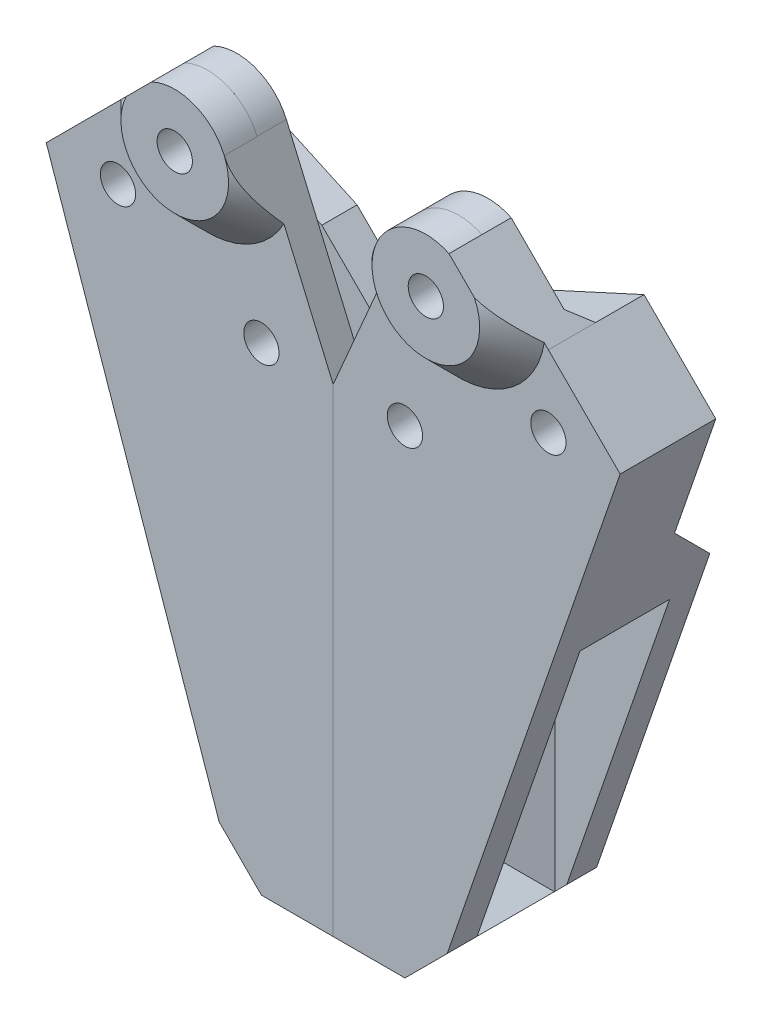
SolidWorks part; units mm, degrees
material "ABS"
ref_plane "Płaszczyzna przednia" through (0, 0, 0) normal (0, 0, 1) x (1, 0, 0)
ref_plane "Płaszczyzna górna" through (0, 0, 0) normal (0, 1, 0) x (1, 0, 0)
ref_plane "Płaszczyzna prawa" through (0, 0, 0) normal (1, 0, 0) x (0, 0, -1)
sketch "Szkic1" plane through (0, 0, 0) normal (0, 0, 1) x (1, 0, 0)
  line L0 (-24, 11) -> (-24, 23)
  line L1 (-24, 11) -> (-36, 11)
  line L2 (-24, 23) -> (-36, 11)
  line L3 (0, 0) -> (0, 12)
  line L4 (0, 12) -> (-24, 23)
  line L5 (0, 0) -> (12, 0)
  line L6 (0, 12) -> (12, 0)
  line L7 (0, 0) -> (0, -80)
  line L8 (0, -80) -> (12, -80)
  line L9 (0, -80) -> (-7.0711, -72.9289)
  line L10 (-7.0711, -72.9289) -> (-36, 11)
  line L11 (12, -80) -> (12, 0)
  circle A0 centre (0, 0) radius 2.95
  circle A1 centre (-24, 11) radius 2.95
  dimension "D1" = 5.9
  dimension "D2" = 24
  dimension "D3" = 5.9
  dimension "D4" = 11
  dimension "D5" = 12
  dimension "D6" = 12
  dimension "D7" = 12
  dimension "D8" = 12
  dimension "D9" = 80
  dimension "D10" = 12
  dimension "D11" = 135
  dimension "D12" = 10
extrude "Dodanie-wyciągnięcie1" add sketch "Szkic1" along normal blind 25 contours A1 L0 L2 L1 | A1 L1 L10 L9 L7 A0 L3 L4 L0 | A0 L5 L6 L3 | A0 L7 L8 L11 L5 region at (-28.2882, 15.2882, 0) region at (-12.4584, -19.8234, 0) region at (4.2882, 4.2882, 0) region at (6.034, -40.2779, 0)
sketch "Szkic3" plane through (12, 0, 0) normal (1, 0, 0) x (0, 0, -1)
  line L0 (-20.1, 17) -> (-20.1, -8)
  line L1 (-25, -80) -> (-25, 0) construction
  line L2 (-14.9, 17) -> (-14.9, -8)
  line L3 (-9, 17) -> (-9, -8)
  line L4 (-4, 17) -> (-4, -8)
  line L5 (0, -80) -> (0, 0) construction
  line L6 (-25, -8) -> (0, -8)
  line L7 (-25, 0) -> (0, 0) construction
  line L8 (-25, 17) -> (0, 17)
  line L9 (-25, 12) -> (-25, 0) construction
  line L10 (0, 12) -> (0, 0) construction
  line M8 (0, 0) -> (-25, 0)
  dimension "D1" = 4.9
  dimension "D2" = 10.1
  dimension "D3" = 4
  dimension "D4" = 9
  dimension "D5" = 8
  dimension "D6" = 25
extrude "Wytnij-wyciągnięcie1" cut sketch "Szkic3" against normal blind 20 contours L8 L0 L2 M8 | L0 L6 L2 M8 | L8 L3 L4 M8 | L3 L6 L4 M8 region at (12, 8.5, 17.5) region at (12, -4, 17.5) region at (12, 8.5, 6.5) region at (12, -4, 6.5)
sketch "Szkic4" plane through (12, 0, 0) normal (1, 0, 0) x (0, 0, -1)
  line L5 (-9, 12) -> (-9, 0) construction
  line L6 (-9, 4) -> (-4, 4)
  line L7 (-9, 4) -> (-9, 23)
  line L8 (-9, 23) -> (-4, 23)
  line L9 (-4, 4) -> (-4, 23)
  line L10 (-25, 23) -> (0, 23) construction
  dimension "D1" = 5
  dimension "D2" = 19
extrude "Wytnij-wyciągnięcie2" cut sketch "Szkic4" against normal blind 58
chamfer "Sfazowanie1" distance 6 angle 45 1 edges at (-8, -8, 17.5)
chamfer "Sfazowanie2" distance 12 angle 45 1 edges at (-8, 4, 6.5)
chamfer "Sfazowanie3" distance 2 angle 30 2 edges at (-8, 6.8333, 14.9) (-8, 6.8333, 20.1) first distance on face at (-8, 6.8333, 17.5)
sketch "Szkic5" plane through (0, 0, 25) normal (0, 0, 1) x (1, 0, 0)
  line L0 (-24, 23) -> (-12.8786, 34.1212)
  line L1 (-24, 23) -> (0, 12)
  line L4 (12, 0) -> (-0.7344, 29.5607)
  line L7 (12, 0) -> (0, 12)
  circle A0 centre (-9, 26) radius 2.95
  arc A5 (-0.7344, 29.5607) -> (-12.8786, 34.1212) centre (-9, 26) ccw
  line M11 (0, 12) -> (-24, 23)
  dimension "D3" = 5.9
  dimension "D1" = 26
  dimension "D2" = 9
extrude "Dodanie-wyciągnięcie2" add sketch "Szkic5" against normal blind 4.9 contours A0 M11 | A0 M11 region at (-6.0366, 21.6949, 25)
sketch "Szkic6" plane through (12, 0, 0) normal (1, 0, 0) x (0, 0, -1)
  line L1 (-9, -8) -> (0, -8)
  line L2 (-9, -8) -> (-9, 23)
  line L3 (-9, 23) -> (0, 23)
  line L4 (0, -8) -> (0, 23)
extrude "Wytnij-wyciągnięcie3" cut sketch "Szkic6" against normal blind 60
chamfer "Sfazowanie4" distance 10 angle 45 1 edges at (-8.7255, -8, 0)
sketch "Szkic8" plane through (0, 0, 25) normal (0, 0, 1) x (1, 0, 0)
  line L0 (-17.1214, 29.8785) -> (-12.8784, 34.1214)
  circle A0 centre (-9, 26) radius 2.95
  arc A1 (-17.1214, 29.8785) -> (-12.8784, 34.1214) centre (-9, 26) ccw
  dimension "D1" = 18
  dimension "D2" = 5.9
extrude "Dodanie-wyciągnięcie3" add sketch "Szkic8" along normal blind 5.5
chamfer "Sfazowanie5" distance 5.5 angle 45 1 edges at (-9.196, 17.0021, 25)
sketch "Szkic10" plane through (12, 0, 0) normal (1, 0, 0) x (0, 0, -1)
  line L0 (-20, -23) -> (-20, -75)
  line L1 (-20, -75) -> (-5, -75)
  line L2 (-5, -75) -> (-5, -23)
  line L3 (-5, -23) -> (-20, -23)
  line L4 (-25, -80) -> (0, -80) construction
  line L5 (0, -80) -> (0, -18) construction
  line L6 (-25, -80) -> (-25, 0) construction
  dimension "D1" = 5
  dimension "D2" = 5
  dimension "D3" = 5
  dimension "D4" = 5
extrude "Wytnij-wyciągnięcie6" cut sketch "Szkic10" against normal blind 70 from offset 5 offset against normal yes
chamfer "Sfazowanie9" distance 7 angle 60 4 edges at (7, -49, 20) (7, -75, 12.5) (7, -49, 5) (7, -23, 12.5) first distance on face at (7, -49, 12.5)
chamfer "Sfazowanie10" distance 3 angle 45 1 edges at (-15.4226, 19.0687, 20.1)
mirror "Lustro1" about plane through (12, 0, 25) normal (-1, 0, 0) of bodies 109
